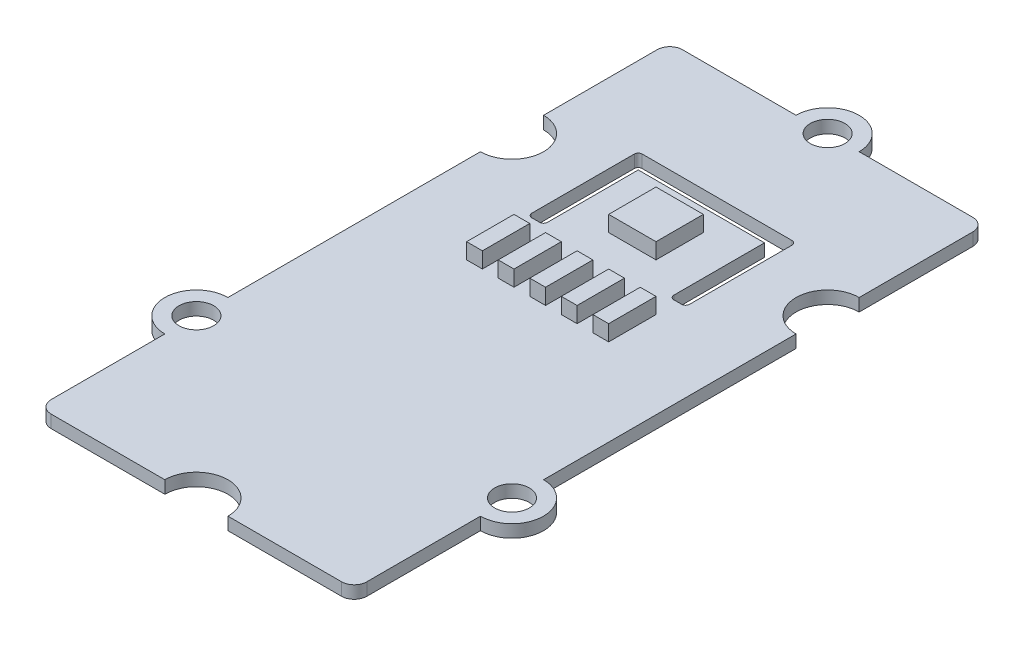
SolidWorks part; units mm, degrees
ref_plane "Front Plane" through (0, 0, 0) normal (0, 0, 1) x (1, 0, 0)
ref_plane "Top Plane" through (0, 0, 0) normal (0, 1, 0) x (1, 0, 0)
ref_plane "Right Plane" through (0, 0, 0) normal (1, 0, 0) x (0, 0, -1)
sketch "Sketch1" plane through (0, 0, 0) normal (0, 1, 0) x (1, 0, 0)
  line L0 (10, 0) -> (10, 40) construction
  line L1 (0.8, 0) -> (8, 0)
  line L2 (0, 0.8) -> (0, 8)
  line L3 (0.8, 40) -> (8, 40)
  line L4 (20, 0.8) -> (20, 8)
  line L5 (12, 40) -> (19.2, 40)
  line L6 (0, 32) -> (0, 39.2)
  line L7 (20, 32) -> (20, 39.2)
  line L8 (0, 12) -> (0, 28)
  line L9 (20, 12) -> (20, 28)
  line L10 (12, 0) -> (19.2, 0)
  arc A0 (0.8, 0) -> (0, 0.8) centre (0.8, 0.8) cw
  arc A1 (19.2, 0) -> (20, 0.8) centre (19.2, 0.8) ccw
  arc A2 (19.2, 40) -> (20, 39.2) centre (19.2, 39.2) cw
  arc A3 (0, 39.2) -> (0.8, 40) centre (0.8, 39.2) cw
  arc A4 (12, 40) -> (8, 40) centre (10, 40) ccw
  circle A5 centre (10, 40) radius 1.1
  arc A6 (0, 28) -> (0, 32) centre (0, 30) ccw
  arc A7 (20, 32) -> (20, 28) centre (20, 30) ccw
  arc A8 (0, 12) -> (0, 8) centre (0, 10) ccw
  arc A9 (20, 8) -> (20, 12) centre (20, 10) ccw
  arc A10 (12, 0) -> (8, 0) centre (10, 0) ccw
  circle A11 centre (0, 10) radius 1.1
  circle A12 centre (20, 10) radius 1.1
  point P7 (0, 0)
  point P10 (20, 0)
  point P13 (20, 40)
  dimension "D3" = 0.8
  dimension "D4" = 2
  dimension "D5" = 2.2
  dimension "D1" = 20
  dimension "D2" = 40
  dimension "D6" = 10
  dimension "D7" = 30
  dimension "D8" = 30
extrude "Board" add sketch "Sketch1" along normal blind 0.8
sketch "Sketch2" plane through (0, 0.8, 0) normal (0, 1, 0) x (1, 0, 0)
  line L0 (14.25, 26) -> (14.75, 26)
  line L1 (5.25, 33) -> (14.75, 33)
  line L2 (5, 32.75) -> (5, 26.25)
  line L3 (5.25, 26) -> (5.75, 26)
  line L4 (15, 32.75) -> (15, 26.25)
  line L6 (6, 26.25) -> (6, 32)
  line L7 (6, 32) -> (14, 32)
  line L8 (14, 26.25) -> (14, 32)
  line L9 (8, 40) -> (0.8, 40) construction
  arc A0 (12, 40) -> (8, 40) centre (10, 40) ccw construction
  arc A1 (5, 26.25) -> (5.25, 26) centre (5.25, 26.25) ccw
  arc A2 (5.75, 26) -> (6, 26.25) centre (5.75, 26.25) ccw
  arc A3 (14.75, 26) -> (15, 26.25) centre (14.75, 26.25) ccw
  arc A4 (14.25, 26) -> (14, 26.25) centre (14.25, 26.25) cw
  arc A5 (14.75, 33) -> (15, 32.75) centre (14.75, 32.75) cw
  arc A6 (5.25, 33) -> (5, 32.75) centre (5.25, 32.75) ccw
  point P8 (10, 32)
  point P9 (10, 33)
  point P10 (5.6543, 32.7865)
  point P14 (10, 42)
  point P19 (5, 26)
  point P22 (6, 26)
  point P25 (15, 26)
  point P30 (15, 33)
  point P33 (5, 33)
  dimension "D6" = 0.25
  dimension "D1" = 1
  dimension "D2" = 1
  dimension "D3" = 7
  dimension "D4" = 10
  dimension "D5" = 7
extrude "U-cut" cut sketch "Sketch2" against normal through all both and the other way through all
sketch "Sketch3" plane through (0, 0.8, 0) normal (0, 1, 0) x (1, 0, 0)
  line L0 (14, 32) -> (6, 32) construction
  line L1 (8.5, 30.625) -> (11.5, 30.625)
  line L2 (8.5, 30.625) -> (8.5, 27.625)
  line L3 (8.5, 27.625) -> (11.5, 27.625)
  line L4 (11.5, 30.625) -> (11.5, 27.625)
  line L5 (9.5, 24.625) -> (10.5, 24.625)
  line L6 (9.5, 24.625) -> (9.5, 21.625)
  line L7 (9.5, 21.625) -> (10.5, 21.625)
  line L8 (10.5, 24.625) -> (10.5, 21.625)
  line L9 (6, 32) -> (6, 26.25) construction
  line L10 (11.5, 24.625) -> (11.5, 21.625)
  line L11 (11.5, 24.625) -> (12.5, 24.625)
  line L12 (12.5, 24.625) -> (12.5, 21.625)
  line L13 (11.5, 21.625) -> (12.5, 21.625)
  line L14 (13.5, 24.625) -> (13.5, 21.625)
  line L15 (13.5, 24.625) -> (14.5, 24.625)
  line L16 (14.5, 24.625) -> (14.5, 21.625)
  line L17 (13.5, 21.625) -> (14.5, 21.625)
  line L18 (9.5, 24.625) -> (9.5, 21.625)
  line L19 (9.5, 24.625) -> (10.5, 24.625)
  line L20 (10.5, 24.625) -> (10.5, 21.625)
  line L21 (9.5, 21.625) -> (10.5, 21.625)
  line L22 (11.5, 24.625) -> (11.5, 21.625)
  line L23 (11.5, 24.625) -> (12.5, 24.625)
  line L24 (12.5, 24.625) -> (12.5, 21.625)
  line L25 (11.5, 21.625) -> (12.5, 21.625)
  line L26 (7.5, 24.625) -> (7.5, 21.625)
  line L27 (7.5, 24.625) -> (8.5, 24.625)
  line L28 (8.5, 24.625) -> (8.5, 21.625)
  line L29 (7.5, 21.625) -> (8.5, 21.625)
  line L30 (9.5, 24.625) -> (9.5, 21.625)
  line L31 (9.5, 24.625) -> (10.5, 24.625)
  line L32 (10.5, 24.625) -> (10.5, 21.625)
  line L33 (9.5, 21.625) -> (10.5, 21.625)
  line L34 (7.5, 24.625) -> (7.5, 21.625)
  line L35 (7.5, 24.625) -> (8.5, 24.625)
  line L36 (8.5, 24.625) -> (8.5, 21.625)
  line L37 (7.5, 21.625) -> (8.5, 21.625)
  line L38 (5.5, 24.625) -> (5.5, 21.625)
  line L39 (5.5, 24.625) -> (6.5, 24.625)
  line L40 (6.5, 24.625) -> (6.5, 21.625)
  line L41 (5.5, 21.625) -> (6.5, 21.625)
  line L42 (9.5, 24.625) -> (11.5, 24.625) construction
  line L43 (9.5, 24.625) -> (7.5, 24.625) construction
  point P10 (10, 32)
  point P11 (10, 30.625)
  point P12 (10, 24.625)
  point P13 (8.5, 29.125)
  point P16 (6, 29.125)
  dimension "D1" = 3
  dimension "D2" = 3
  dimension "D3" = 1
  dimension "D4" = 3
  dimension "D5" = 3
  dimension "D8" = 2
  dimension "D9" = 2
  dimension "D6" = 3
  dimension "D7" = 3
extrude "SMDs" add sketch "Sketch3" along normal blind 1 contours L38 L41 L40 L39 | L26 L29 L28 L27 | L8 L5 L6 L7 | L10 L13 L12 L11 | L14 L17 L16 L15 | L4 L1 L2 L3 region at (10, 0.8, -29.125) region at (10, 0.8, -23.125) region at (12, 0.8, -23.125) region at (14, 0.8, -23.125) region at (8, 0.8, -23.125) region at (6, 0.8, -23.125)
